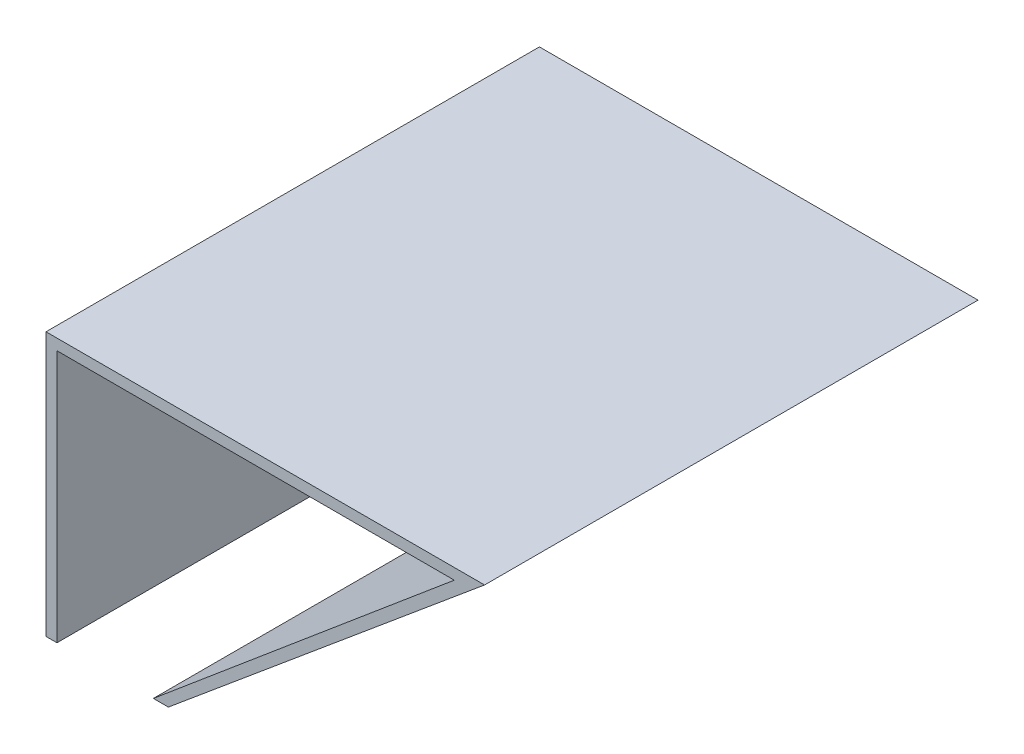
SolidWorks part; units mm, degrees
ref_plane "Front Plane" through (0, 0, 0) normal (0, 0, 1) x (1, 0, 0)
ref_plane "Top Plane" through (0, 0, 0) normal (0, 1, 0) x (1, 0, 0)
ref_plane "Right Plane" through (0, 0, 0) normal (1, 0, 0) x (0, 0, -1)
sketch "Sketch1" plane through (0, 0, 0) normal (0, 0, 1) x (1, 0, 0)
  line L1 (11.1602, 0) -> (40, 24.066)
  line L2 (40, 24.066) -> (0, 24.066)
  line L3 (0, 24.066) -> (0, 0)
  line L4 (1, 23.066) -> (1, 0)
  line L6 (9.7882, 0) -> (37.2408, 23.066)
  line L7 (37.2408, 23.066) -> (1, 23.066)
  line L10 (0, 0) -> (1, 0)
  line L11 (9.7882, 0) -> (11.1602, 0)
  point P4 (0, 0)
  point P7 (9.8055, 0)
  point P10 (0, 0)
  point P11 (0, 0)
  point P12 (0, 0)
  point P13 (1, 1)
  point P14 (0, 0)
  point P15 (0, 0)
  point P16 (0, 0)
  point P18 (9.7882, 0)
  dimension "D2" = 40
  dimension "D1" = 1
  dimension "D3" = 1
extrude "Boss-Extrude1" add sketch "Sketch1" along normal blind 45
